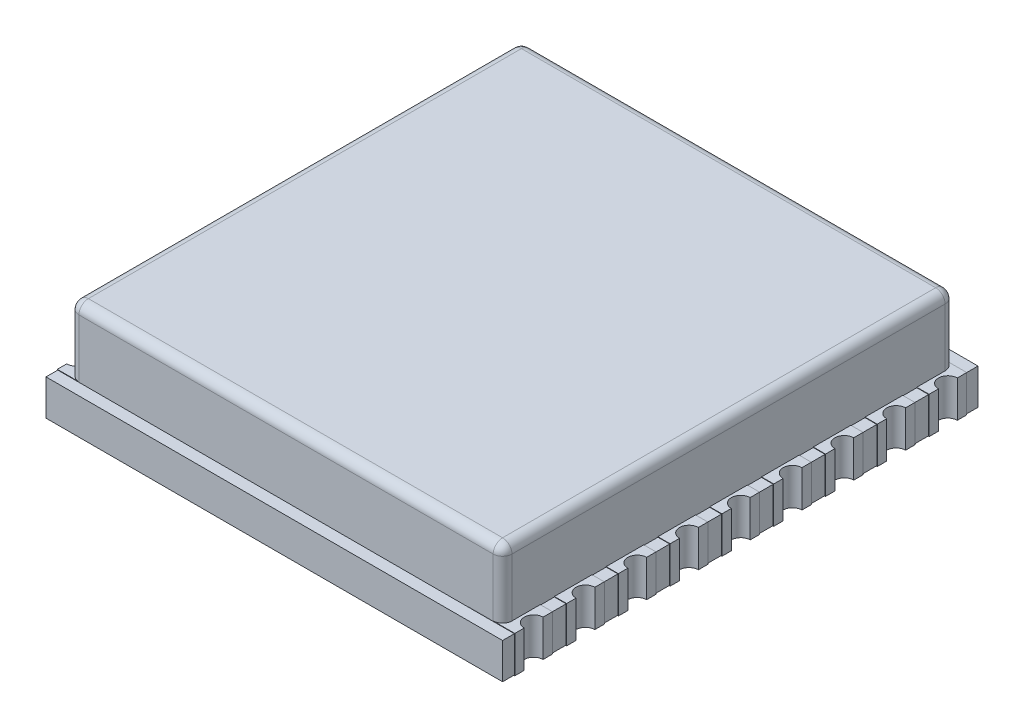
SolidWorks part; units mm, degrees
ref_plane "Front Plane" through (0, 0, 0) normal (0, 0, 1) x (1, 0, 0)
ref_plane "Top Plane" through (0, 0, 0) normal (0, 1, 0) x (1, 0, 0)
ref_plane "Right Plane" through (0, 0, 0) normal (1, 0, 0) x (0, 0, -1)
sketch "Sketch1" plane through (0, 0, 0) normal (0, 1, 0) x (1, 0, 0)
  line L1 (-4.85, -5.05) -> (4.85, -5.05)
  line L2 (-4.85, -5.05) -> (-4.85, 5.05)
  line L3 (-4.85, 5.05) -> (4.85, 5.05)
  line L4 (4.85, -5.05) -> (4.85, 5.05)
  line L5 (-4.85, -5.05) -> (4.85, 5.05) construction
  line L6 (-4.85, 5.05) -> (4.85, -5.05) construction
  point P0 (0, 0)
  dimension "D1" = 9.7
  dimension "D2" = 10.1
extrude "Boss-Extrude1" add sketch "Sketch1" along normal blind 0.76
sketch "Sketch2" plane through (0, 0.76, 0) normal (0, 1, 0) x (1, 0, 0)
  line L0 (-4.85, 5.05) -> (-4.85, -5.05) construction
  line L1 (4.85, 5.05) -> (-4.85, 5.05) construction
  line L2 (0, 5.05) -> (0, -5.05) construction
  line L3 (-4.85, -5.05) -> (4.85, -5.05) construction
  circle A0 centre (-4.85, 4.4) radius 0.25
  circle A1 centre (-4.85, 3.3) radius 0.25
  circle A2 centre (-4.85, 2.2) radius 0.25
  circle A3 centre (-4.85, 1.1) radius 0.25
  circle A4 centre (-4.85, 0) radius 0.25
  circle A5 centre (-4.85, -1.1) radius 0.25
  circle A6 centre (-4.85, -2.2) radius 0.25
  circle A7 centre (-4.85, -3.3) radius 0.25
  circle A8 centre (-4.85, -4.4) radius 0.25
  circle A9 centre (4.85, -4.4) radius 0.25
  circle A10 centre (4.85, -3.3) radius 0.25
  circle A11 centre (4.85, -2.2) radius 0.25
  circle A12 centre (4.85, -1.1) radius 0.25
  circle A13 centre (4.85, 0) radius 0.25
  circle A14 centre (4.85, 1.1) radius 0.25
  circle A15 centre (4.85, 2.2) radius 0.25
  circle A16 centre (4.85, 3.3) radius 0.25
  circle A17 centre (4.85, 4.4) radius 0.25
  dimension "D1" = 0.5
  dimension "D2" = 0.65
  dimension "D4" = 0.65
  dimension "D3" = 9
extrude "Cut-Extrude1" cut sketch "Sketch2" against normal up to next
sketch "Sketch3" plane through (0, 0.76, 0) normal (0, 1, 0) x (1, 0, 0)
  line L0 (-4.6, 4.4) -> (4.6, 4.4) construction
  line L2 (-3.86, 4) -> (-4.86, 4)
  line L3 (-3.86, 4) -> (-3.86, 4.8)
  line L4 (-3.86, 4.8) -> (-4.86, 4.8)
  line L5 (-4.86, 4) -> (-4.86, 4.8)
  line L6 (-3.86, 4) -> (-4.86, 4.8) construction
  line L7 (-3.86, 4.8) -> (-4.86, 4) construction
  line L8 (0, 5.05) -> (0, -5.05) construction
  line L9 (4.85, 5.05) -> (-4.85, 5.05) construction
  line L10 (-4.85, -5.05) -> (4.85, -5.05) construction
  line L11 (-3.86, 2.9) -> (-3.86, 3.7)
  line L12 (-3.86, 2.9) -> (-4.86, 2.9)
  line L13 (-4.86, 2.9) -> (-4.86, 3.7)
  line L14 (-3.86, 3.7) -> (-4.86, 3.7)
  line L15 (-3.86, 1.8) -> (-3.86, 2.6)
  line L16 (-3.86, 1.8) -> (-4.86, 1.8)
  line L17 (-4.86, 1.8) -> (-4.86, 2.6)
  line L18 (-3.86, 2.6) -> (-4.86, 2.6)
  line L19 (-3.86, 0.7) -> (-3.86, 1.5)
  line L20 (-3.86, 0.7) -> (-4.86, 0.7)
  line L21 (-4.86, 0.7) -> (-4.86, 1.5)
  line L22 (-3.86, 1.5) -> (-4.86, 1.5)
  line L23 (-3.86, -0.4) -> (-3.86, 0.4)
  line L24 (-3.86, -0.4) -> (-4.86, -0.4)
  line L25 (-4.86, -0.4) -> (-4.86, 0.4)
  line L26 (-3.86, 0.4) -> (-4.86, 0.4)
  line L27 (-3.86, -1.5) -> (-3.86, -0.7)
  line L28 (-3.86, -1.5) -> (-4.86, -1.5)
  line L29 (-4.86, -1.5) -> (-4.86, -0.7)
  line L30 (-3.86, -0.7) -> (-4.86, -0.7)
  line L31 (-3.86, -2.6) -> (-3.86, -1.8)
  line L32 (-3.86, -2.6) -> (-4.86, -2.6)
  line L33 (-4.86, -2.6) -> (-4.86, -1.8)
  line L34 (-3.86, -1.8) -> (-4.86, -1.8)
  line L35 (-3.86, -3.7) -> (-3.86, -2.9)
  line L36 (-3.86, -3.7) -> (-4.86, -3.7)
  line L37 (-4.86, -3.7) -> (-4.86, -2.9)
  line L38 (-3.86, -2.9) -> (-4.86, -2.9)
  line L39 (-3.86, -4.8) -> (-3.86, -4)
  line L40 (-3.86, -4.8) -> (-4.86, -4.8)
  line L41 (-4.86, -4.8) -> (-4.86, -4)
  line L42 (-3.86, -4) -> (-4.86, -4)
  line L43 (3.86, -4) -> (4.86, -4)
  line L44 (4.86, -4.8) -> (4.86, -4)
  line L45 (3.86, -4.8) -> (4.86, -4.8)
  line L46 (3.86, -4.8) -> (3.86, -4)
  line L47 (3.86, -2.9) -> (4.86, -2.9)
  line L48 (4.86, -3.7) -> (4.86, -2.9)
  line L49 (3.86, -3.7) -> (4.86, -3.7)
  line L50 (3.86, -3.7) -> (3.86, -2.9)
  line L51 (3.86, -1.8) -> (4.86, -1.8)
  line L52 (4.86, -2.6) -> (4.86, -1.8)
  line L53 (3.86, -2.6) -> (4.86, -2.6)
  line L54 (3.86, -2.6) -> (3.86, -1.8)
  line L55 (3.86, -0.7) -> (4.86, -0.7)
  line L56 (4.86, -1.5) -> (4.86, -0.7)
  line L57 (3.86, -1.5) -> (4.86, -1.5)
  line L58 (3.86, -1.5) -> (3.86, -0.7)
  line L59 (3.86, 0.4) -> (4.86, 0.4)
  line L60 (4.86, -0.4) -> (4.86, 0.4)
  line L61 (3.86, -0.4) -> (4.86, -0.4)
  line L62 (3.86, -0.4) -> (3.86, 0.4)
  line L63 (3.86, 1.5) -> (4.86, 1.5)
  line L64 (4.86, 0.7) -> (4.86, 1.5)
  line L65 (3.86, 0.7) -> (4.86, 0.7)
  line L66 (3.86, 0.7) -> (3.86, 1.5)
  line L67 (3.86, 2.6) -> (4.86, 2.6)
  line L68 (4.86, 1.8) -> (4.86, 2.6)
  line L69 (3.86, 1.8) -> (4.86, 1.8)
  line L70 (3.86, 1.8) -> (3.86, 2.6)
  line L71 (3.86, 3.7) -> (4.86, 3.7)
  line L72 (4.86, 2.9) -> (4.86, 3.7)
  line L73 (3.86, 2.9) -> (4.86, 2.9)
  line L74 (3.86, 2.9) -> (3.86, 3.7)
  line L75 (4.86, 4) -> (4.86, 4.8)
  line L76 (3.86, 4.8) -> (4.86, 4.8)
  line L77 (3.86, 4) -> (3.86, 4.8)
  line L78 (3.86, 4) -> (4.86, 4)
  line L79 (-4.85, 5.05) -> (-4.85, 4.65) construction
  arc A0 (-4.85, 4.15) -> (-4.85, 4.65) centre (-4.85, 4.4) ccw construction
  arc A1 (4.85, 4.65) -> (4.85, 4.15) centre (4.85, 4.4) ccw construction
  point P8 (-4.36, 4.4)
  dimension "D1" = 0.8
  dimension "D2" = 1
  dimension "D4" = 0.25
  dimension "D5" = 0.01
  dimension "D3" = 9
extrude "Boss-Extrude2" add sketch "Sketch3" against normal blind 0.78 from offset 0.01 separate body
sketch "Sketch4" plane through (0, 0.77, 0) normal (0, 1, 0) x (1, 0, 0)
  line L0 (-4.86, 4.8) -> (-4.86, 4) construction
  line L1 (-4.85, -5.05) -> (4.85, -5.05) construction
  line L2 (0, 5.05) -> (0, -5.05) construction
  line L3 (4.85, 5.05) -> (-4.85, 5.05) construction
  circle A0 centre (-4.86, 4.4) radius 0.2
  circle A1 centre (-4.86, 3.3) radius 0.2
  circle A2 centre (-4.86, 2.2) radius 0.2
  circle A3 centre (-4.86, 1.1) radius 0.2
  circle A4 centre (-4.86, 0) radius 0.2
  circle A5 centre (-4.86, -1.1) radius 0.2
  circle A6 centre (-4.86, -2.2) radius 0.2
  circle A7 centre (-4.86, -3.3) radius 0.2
  circle A8 centre (-4.86, -4.4) radius 0.2
  circle A9 centre (4.86, -4.4) radius 0.2
  circle A10 centre (4.86, -3.3) radius 0.2
  circle A11 centre (4.86, -2.2) radius 0.2
  circle A12 centre (4.86, -1.1) radius 0.2
  circle A13 centre (4.86, 0) radius 0.2
  circle A14 centre (4.86, 1.1) radius 0.2
  circle A15 centre (4.86, 2.2) radius 0.2
  circle A16 centre (4.86, 3.3) radius 0.2
  circle A17 centre (4.86, 4.4) radius 0.2
  dimension "D1" = 0.4
  dimension "D3" = 0.65
  dimension "D2" = 9
extrude "Cut-Extrude2" cut sketch "Sketch4" against normal through all
sketch "Sketch5" plane through (0, 0.76, 0) normal (0, 1, 0) x (1, 0, 0)
  line L1 (-4.6, -4.8) -> (4.6, -4.8)
  line L2 (-4.6, -4.8) -> (-4.6, 4.8)
  line L3 (-4.6, 4.8) -> (4.6, 4.8)
  line L4 (4.6, -4.8) -> (4.6, 4.8)
  line L5 (-4.6, -4.8) -> (4.6, 4.8) construction
  line L6 (-4.6, 4.8) -> (4.6, -4.8) construction
  point P0 (0, 0)
  dimension "D1" = 9.2
  dimension "D2" = 9.6
extrude "Boss-Extrude3" add sketch "Sketch5" along normal blind 1.44 separate body
fillet "Fillet1" radius 0.2 8 edges at (0, 2.2, 4.8) (-4.6, 2.2, 0) (0, 2.2, -4.8) (4.6, 2.2, 0) (-4.6, 1.48, -4.8) (4.6, 1.48, -4.8) (4.6, 1.48, 4.8) (-4.6, 1.48, 4.8)
shell "Shell1" thickness 0.2 removed face at (0, 0.76, 0)
